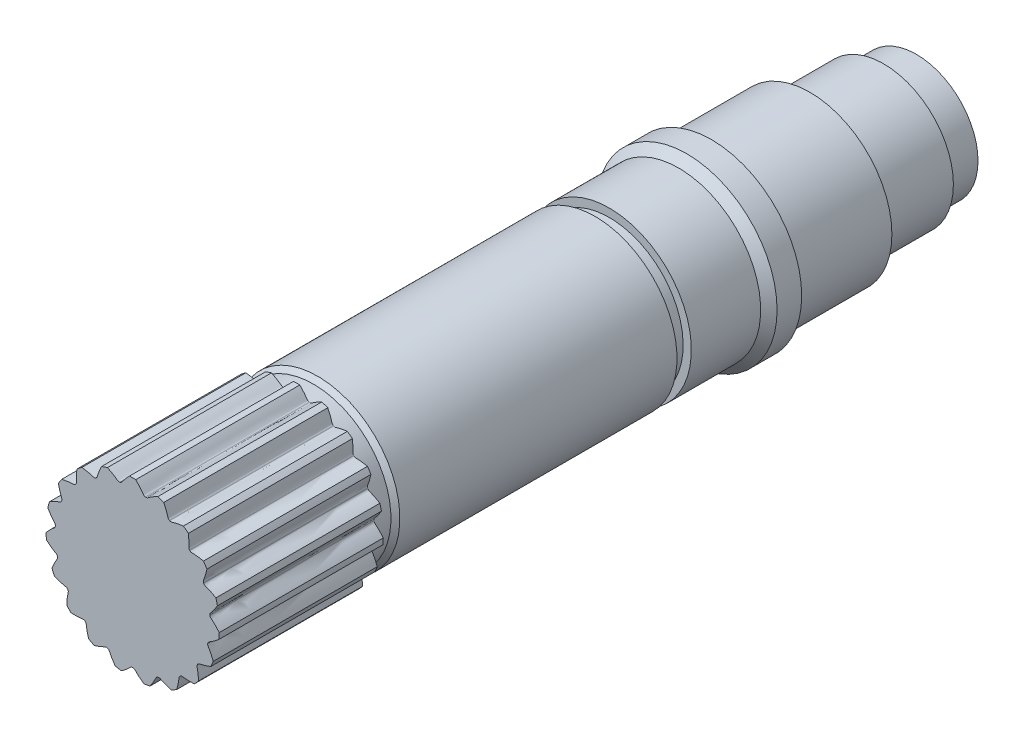
SolidWorks part; units mm, degrees
material "Alloy Steel"
ref_plane "Front Plane" through (0, 0, 0) normal (0, 0, 1) x (1, 0, 0)
ref_plane "Top Plane" through (0, 0, 0) normal (0, 1, 0) x (1, 0, 0)
ref_plane "Right Plane" through (0, 0, 0) normal (1, 0, 0) x (0, 0, -1)
sketch "Sketch12" plane through (0, 0, 0) normal (0, 0, 1) x (1, 0, 0)
  circle A0 centre (0, 0) radius 10
  dimension "D1" = 20
extrude "Shaft" add sketch "Sketch12" along normal mid plane 45
sketch "Sketch13" plane through (0, 0, 22.5) normal (0, 0, 1) x (1, 0, 0)
  circle A0 centre (0, 0) radius 9.4556
  dimension "D1" = 18.9113
extrude "Motor side relief" add sketch "Sketch13" along normal blind 1.587
sketch "Sketch14" plane through (0, 0, -22.5) normal (0, 0, -1) x (-1, 0, 0)
  circle A0 centre (0, 0) radius 8.3981
  dimension "D1" = 16.7963
sketch "Sketch15" plane through (0, 0, 24.087) normal (0, 0, 1) x (1, 0, 0)
  line L0 (5.7898, -7.4758) -> (5.8078, -7.4618)
  line L1 (5.8078, -7.4618) -> (5.8257, -7.4478)
  line L2 (7.9035, -5.1908) -> (7.9159, -5.1717)
  line L3 (7.9159, -5.1717) -> (7.9284, -5.1527)
  line L4 (9.1607, -2.3432) -> (9.1663, -2.3212)
  line L5 (9.1663, -2.3212) -> (9.1719, -2.2992)
  line L6 (9.4252, 0.7582) -> (9.4233, 0.7808)
  line L7 (9.4233, 0.7808) -> (9.4214, 0.8035)
  line L8 (8.6683, 3.7775) -> (8.6592, 3.7983)
  line L9 (8.6592, 3.7983) -> (8.6501, 3.8191)
  line L10 (6.9721, 6.3874) -> (6.9567, 6.4041)
  line L11 (6.9567, 6.4041) -> (6.9413, 6.4208)
  line L12 (4.5204, 8.3051) -> (4.5004, 8.316)
  line L13 (4.5004, 8.316) -> (4.4804, 8.3268)
  line L14 (1.5788, 9.3229) -> (1.5563, 9.3267)
  line L15 (1.5563, 9.3267) -> (1.5339, 9.3304)
  line L16 (-1.5339, 9.3304) -> (-1.5563, 9.3267)
  line L17 (-1.5563, 9.3267) -> (-1.5788, 9.3229)
  line L18 (-4.4804, 8.3268) -> (-4.5004, 8.316)
  line L19 (-4.5004, 8.316) -> (-4.5204, 8.3051)
  line L20 (-6.9413, 6.4208) -> (-6.9567, 6.4041)
  line L21 (-6.9567, 6.4041) -> (-6.9721, 6.3874)
  line L22 (-8.6501, 3.8191) -> (-8.6592, 3.7983)
  line L23 (-8.6592, 3.7983) -> (-8.6683, 3.7775)
  line L24 (-9.4214, 0.8035) -> (-9.4233, 0.7808)
  line L25 (-9.4233, 0.7808) -> (-9.4252, 0.7582)
  line L26 (-9.1719, -2.2992) -> (-9.1663, -2.3212)
  line L27 (-9.1663, -2.3212) -> (-9.1607, -2.3432)
  line L28 (-7.9284, -5.1527) -> (-7.9159, -5.1717)
  line L29 (-7.9159, -5.1717) -> (-7.9035, -5.1908)
  line L30 (-5.8257, -7.4478) -> (-5.8078, -7.4618)
  line L31 (-5.8078, -7.4618) -> (-5.7898, -7.4758)
  line L32 (-3.0917, -8.9359) -> (-3.0702, -8.9433)
  line L33 (-3.0702, -8.9433) -> (-3.0487, -8.9507)
  line L34 (-0.0227, -9.4556) -> (0, -9.4556)
  line L35 (0, -9.4556) -> (0.0227, -9.4556)
  line L36 (3.0487, -8.9507) -> (3.0702, -8.9433)
  line L37 (3.0702, -8.9433) -> (3.0917, -8.9359)
  arc A0 (4.6925, -9.4774) -> (5.3676, -9.1121) centre (0, 0) ccw
  arc A1 (7.5156, -7.4402) -> (8.0355, -6.8755) centre (0, 0) ccw
  arc A2 (9.5242, -4.5968) -> (9.8326, -3.8939) centre (0, 0) ccw
  arc A3 (10.5007, -1.2552) -> (10.5641, -0.4903) centre (0, 0) ccw
  arc A4 (10.3394, 2.2224) -> (10.1509, 2.9665) centre (0, 0) ccw
  arc A5 (9.0575, 5.4591) -> (8.6377, 6.1017) centre (0, 0) ccw
  arc A6 (6.7942, 8.1043) -> (6.1885, 8.5758) centre (0, 0) ccw
  arc A7 (3.7946, 9.8713) -> (3.0686, 10.1205) centre (0, 0) ccw
  arc A8 (0.3838, 10.5685) -> (-0.3838, 10.5685) centre (0, 0) ccw
  arc A9 (-3.0686, 10.1205) -> (-3.7946, 9.8713) centre (0, 0) ccw
  arc A10 (-6.1885, 8.5758) -> (-6.7942, 8.1043) centre (0, 0) ccw
  arc A11 (-8.6377, 6.1017) -> (-9.0575, 5.4591) centre (0, 0) ccw
  arc A12 (-10.1509, 2.9665) -> (-10.3394, 2.2224) centre (0, 0) ccw
  arc A13 (-10.5641, -0.4903) -> (-10.5007, -1.2552) centre (0, 0) ccw
  arc A14 (-9.8326, -3.8939) -> (-9.5242, -4.5968) centre (0, 0) ccw
  arc A15 (-8.0355, -6.8755) -> (-7.5156, -7.4402) centre (0, 0) ccw
  arc A16 (-5.3676, -9.1121) -> (-4.6925, -9.4774) centre (0, 0) ccw
  arc A17 (-2.1181, -10.3612) -> (-1.361, -10.4876) centre (0, 0) ccw
  arc A18 (1.361, -10.4876) -> (2.1181, -10.3612) centre (0, 0) ccw
  spline S0 degree 3 poles (3.0917, -8.9359) (3.1544, -8.9142) (3.2184, -8.911) (3.3396, -8.938) (3.397, -8.9729) (3.5767, -9.0624) (3.828, -9.1783) (4.24, -9.3384) (4.5379, -9.4334) (4.6925, -9.4774) knots 0 0 0 0 0.125 0.125 0.25 0.25 0.5 0.75 1 1 1 1
  spline S1 degree 3 poles (5.3676, -9.1121) (5.4153, -8.9586) (5.4987, -8.6572) (5.5901, -8.2247) (5.6305, -7.951) (5.6538, -7.7516) (5.656, -7.6845) (5.6997, -7.5682) (5.7374, -7.5164) (5.7898, -7.4758) knots 0 0 0 0 0.25 0.5 0.75 0.75 0.875 0.875 1 1 1 1
  spline S2 degree 3 poles (5.8257, -7.4478) (5.8779, -7.407) (5.9374, -7.3832) (6.0608, -7.3694) (6.1265, -7.3837) (6.3255, -7.41) (6.6008, -7.438) (7.0425, -7.4557) (7.3551, -7.4488) (7.5156, -7.4402) knots 0 0 0 0 0.125 0.125 0.25 0.25 0.5 0.75 1 1 1 1
  spline S3 degree 3 poles (8.0355, -6.8755) (8.0308, -6.7148) (8.0117, -6.4027) (7.9577, -5.964) (7.9071, -5.692) (7.8645, -5.4958) (7.8447, -5.4316) (7.8483, -5.3075) (7.8671, -5.2462) (7.9035, -5.1908) knots 0 0 0 0 0.25 0.5 0.75 0.75 0.875 0.875 1 1 1 1
  spline S4 degree 3 poles (7.9284, -5.1527) (7.9645, -5.0971) (8.013, -5.0552) (8.1253, -5.0021) (8.192, -4.9944) (8.3888, -4.9546) (8.6583, -4.8918) (9.0817, -4.765) (9.3752, -4.6571) (9.5242, -4.5968) knots 0 0 0 0 0.125 0.125 0.25 0.25 0.5 0.75 1 1 1 1
  spline S5 degree 3 poles (9.8326, -3.8939) (9.7759, -3.7434) (9.6566, -3.4544) (9.4631, -3.057) (9.3268, -2.8161) (9.2228, -2.6445) (9.1833, -2.5901) (9.1463, -2.4716) (9.1443, -2.4075) (9.1607, -2.3432) knots 0 0 0 0 0.25 0.5 0.75 0.75 0.875 0.875 1 1 1 1
  spline S6 degree 3 poles (9.1719, -2.2992) (9.188, -2.2349) (9.2203, -2.1795) (9.3092, -2.0928) (9.3699, -2.0638) (9.543, -1.9624) (9.7775, -1.8154) (10.1368, -1.558) (10.3793, -1.3606) (10.5007, -1.2552) knots 0 0 0 0 0.125 0.125 0.25 0.25 0.5 0.75 1 1 1 1
  spline S7 degree 3 poles (10.5641, -0.4903) (10.4617, -0.3663) (10.255, -0.1317) (9.9429, 0.1813) (9.7359, 0.3649) (9.5818, 0.4935) (9.5267, 0.532) (9.4533, 0.6322) (9.4305, 0.6921) (9.4252, 0.7582) knots 0 0 0 0 0.25 0.5 0.75 0.75 0.875 0.875 1 1 1 1
  spline S8 degree 3 poles (9.4214, 0.8035) (9.4158, 0.8695) (9.4284, 0.9324) (9.4844, 1.0433) (9.5323, 1.0904) (9.6631, 1.2426) (9.8372, 1.4577) (10.0935, 1.8179) (10.2588, 2.0833) (10.3394, 2.2224) knots 0 0 0 0 0.125 0.125 0.25 0.25 0.5 0.75 1 1 1 1
  spline S9 degree 3 poles (10.1509, 2.9665) (10.0138, 3.0504) (9.7422, 3.2052) (9.3453, 3.4) (9.0899, 3.5063) (8.9024, 3.5779) (8.8378, 3.5965) (8.7358, 3.6674) (8.6948, 3.7167) (8.6683, 3.7775) knots 0 0 0 0 0.25 0.5 0.75 0.75 0.875 0.875 1 1 1 1
  spline S10 degree 3 poles (8.6501, 3.8191) (8.6233, 3.8797) (8.6148, 3.9433) (8.6317, 4.0663) (8.6618, 4.1264) (8.7361, 4.3129) (8.8308, 4.5729) (8.9563, 4.9967) (9.0265, 5.3014) (9.0575, 5.4591) knots 0 0 0 0 0.125 0.125 0.25 0.25 0.5 0.75 1 1 1 1
  spline S11 degree 3 poles (8.6377, 6.1017) (8.4808, 6.1366) (8.1736, 6.1948) (7.735, 6.2502) (7.4588, 6.2678) (7.2583, 6.2747) (7.1911, 6.2713) (7.0717, 6.3052) (7.0169, 6.3385) (6.9721, 6.3874) knots 0 0 0 0 0.25 0.5 0.75 0.75 0.875 0.875 1 1 1 1
  spline S12 degree 3 poles (6.9413, 6.4208) (6.8963, 6.4695) (6.8676, 6.5268) (6.8437, 6.6487) (6.8526, 6.7153) (6.8624, 6.9158) (6.8676, 7.1925) (6.8486, 7.6341) (6.816, 7.9451) (6.7942, 8.1043) knots 0 0 0 0 0.125 0.125 0.25 0.25 0.5 0.75 1 1 1 1
  spline S13 degree 3 poles (6.1885, 8.5758) (6.0287, 8.5578) (5.7193, 8.5131) (5.2865, 8.4231) (5.0196, 8.3501) (4.8276, 8.2914) (4.7652, 8.2664) (4.6412, 8.2597) (4.5786, 8.2734) (4.5204, 8.3051) knots 0 0 0 0 0.25 0.5 0.75 0.75 0.875 0.875 1 1 1 1
  spline S14 degree 3 poles (4.4804, 8.3268) (4.422, 8.3582) (4.3763, 8.4031) (4.3141, 8.5106) (4.3009, 8.5765) (4.245, 8.7693) (4.1601, 9.0326) (3.9988, 9.4442) (3.8669, 9.7277) (3.7946, 9.8713) knots 0 0 0 0 0.125 0.125 0.25 0.25 0.5 0.75 1 1 1 1
  spline S15 degree 3 poles (3.0686, 10.1205) (2.9233, 10.0517) (2.6452, 9.9089) (2.2651, 9.6832) (2.0363, 9.5275) (1.8738, 9.4097) (1.8229, 9.3658) (1.7078, 9.3192) (1.6441, 9.3118) (1.5788, 9.3229) knots 0 0 0 0 0.25 0.5 0.75 0.75 0.875 0.875 1 1 1 1
  spline S16 degree 3 poles (1.5339, 9.3304) (1.4685, 9.3411) (1.4107, 9.3688) (1.3169, 9.4502) (1.283, 9.5083) (1.1676, 9.6725) (1.0018, 9.894) (0.7156, 10.2309) (0.4988, 10.4563) (0.3838, 10.5685) knots 0 0 0 0 0.125 0.125 0.25 0.25 0.5 0.75 1 1 1 1
  spline S17 degree 3 poles (-0.3838, 10.5685) (-0.4988, 10.4563) (-0.7156, 10.2309) (-1.0018, 9.894) (-1.1676, 9.6725) (-1.283, 9.5083) (-1.3169, 9.4502) (-1.4107, 9.3688) (-1.4685, 9.3411) (-1.5339, 9.3304) knots 0 0 0 0 0.25 0.5 0.75 0.75 0.875 0.875 1 1 1 1
  spline S18 degree 3 poles (-1.5788, 9.3229) (-1.6441, 9.3118) (-1.7078, 9.3192) (-1.8229, 9.3658) (-1.8738, 9.4097) (-2.0363, 9.5275) (-2.2651, 9.6832) (-2.6452, 9.9089) (-2.9233, 10.0517) (-3.0686, 10.1205) knots 0 0 0 0 0.125 0.125 0.25 0.25 0.5 0.75 1 1 1 1
  spline S19 degree 3 poles (-3.7946, 9.8713) (-3.8669, 9.7277) (-3.9988, 9.4442) (-4.1601, 9.0326) (-4.245, 8.7693) (-4.3009, 8.5765) (-4.3141, 8.5106) (-4.3763, 8.4031) (-4.422, 8.3582) (-4.4804, 8.3268) knots 0 0 0 0 0.25 0.5 0.75 0.75 0.875 0.875 1 1 1 1
  spline S20 degree 3 poles (-4.5204, 8.3051) (-4.5786, 8.2734) (-4.6412, 8.2597) (-4.7652, 8.2664) (-4.8276, 8.2914) (-5.0196, 8.3501) (-5.2865, 8.4231) (-5.7193, 8.5131) (-6.0287, 8.5578) (-6.1885, 8.5758) knots 0 0 0 0 0.125 0.125 0.25 0.25 0.5 0.75 1 1 1 1
  spline S21 degree 3 poles (-6.7942, 8.1043) (-6.816, 7.9451) (-6.8486, 7.6341) (-6.8676, 7.1925) (-6.8624, 6.9158) (-6.8526, 6.7153) (-6.8437, 6.6487) (-6.8676, 6.5268) (-6.8963, 6.4695) (-6.9413, 6.4208) knots 0 0 0 0 0.25 0.5 0.75 0.75 0.875 0.875 1 1 1 1
  spline S22 degree 3 poles (-6.9721, 6.3874) (-7.0169, 6.3385) (-7.0717, 6.3052) (-7.1911, 6.2713) (-7.2583, 6.2747) (-7.4588, 6.2678) (-7.735, 6.2502) (-8.1736, 6.1948) (-8.4808, 6.1366) (-8.6377, 6.1017) knots 0 0 0 0 0.125 0.125 0.25 0.25 0.5 0.75 1 1 1 1
  spline S23 degree 3 poles (-9.0575, 5.4591) (-9.0265, 5.3014) (-8.9563, 4.9967) (-8.8308, 4.5729) (-8.7361, 4.3129) (-8.6618, 4.1264) (-8.6317, 4.0663) (-8.6148, 3.9433) (-8.6233, 3.8797) (-8.6501, 3.8191) knots 0 0 0 0 0.25 0.5 0.75 0.75 0.875 0.875 1 1 1 1
  spline S24 degree 3 poles (-8.6683, 3.7775) (-8.6948, 3.7167) (-8.7358, 3.6674) (-8.8378, 3.5965) (-8.9024, 3.5779) (-9.0899, 3.5063) (-9.3453, 3.4) (-9.7422, 3.2052) (-10.0138, 3.0504) (-10.1509, 2.9665) knots 0 0 0 0 0.125 0.125 0.25 0.25 0.5 0.75 1 1 1 1
  spline S25 degree 3 poles (-10.3394, 2.2224) (-10.2588, 2.0833) (-10.0935, 1.8179) (-9.8372, 1.4577) (-9.6631, 1.2426) (-9.5323, 1.0904) (-9.4844, 1.0433) (-9.4284, 0.9324) (-9.4158, 0.8695) (-9.4214, 0.8035) knots 0 0 0 0 0.25 0.5 0.75 0.75 0.875 0.875 1 1 1 1
  spline S26 degree 3 poles (-9.4252, 0.7582) (-9.4305, 0.6921) (-9.4533, 0.6322) (-9.5267, 0.532) (-9.5818, 0.4935) (-9.7359, 0.3649) (-9.9429, 0.1813) (-10.255, -0.1317) (-10.4617, -0.3663) (-10.5641, -0.4903) knots 0 0 0 0 0.125 0.125 0.25 0.25 0.5 0.75 1 1 1 1
  spline S27 degree 3 poles (-10.5007, -1.2552) (-10.3793, -1.3606) (-10.1368, -1.558) (-9.7775, -1.8154) (-9.543, -1.9624) (-9.3699, -2.0638) (-9.3092, -2.0928) (-9.2203, -2.1795) (-9.188, -2.2349) (-9.1719, -2.2992) knots 0 0 0 0 0.25 0.5 0.75 0.75 0.875 0.875 1 1 1 1
  spline S28 degree 3 poles (-9.1607, -2.3432) (-9.1443, -2.4075) (-9.1463, -2.4716) (-9.1833, -2.5901) (-9.2228, -2.6445) (-9.3268, -2.8161) (-9.4631, -3.057) (-9.6566, -3.4544) (-9.7759, -3.7434) (-9.8326, -3.8939) knots 0 0 0 0 0.125 0.125 0.25 0.25 0.5 0.75 1 1 1 1
  spline S29 degree 3 poles (-9.5242, -4.5968) (-9.3752, -4.6571) (-9.0817, -4.765) (-8.6583, -4.8918) (-8.3888, -4.9546) (-8.192, -4.9944) (-8.1253, -5.0021) (-8.013, -5.0552) (-7.9645, -5.0971) (-7.9284, -5.1527) knots 0 0 0 0 0.25 0.5 0.75 0.75 0.875 0.875 1 1 1 1
  spline S30 degree 3 poles (-7.9035, -5.1908) (-7.8671, -5.2462) (-7.8483, -5.3075) (-7.8447, -5.4316) (-7.8645, -5.4958) (-7.9071, -5.692) (-7.9577, -5.964) (-8.0117, -6.4027) (-8.0308, -6.7148) (-8.0355, -6.8755) knots 0 0 0 0 0.125 0.125 0.25 0.25 0.5 0.75 1 1 1 1
  spline S31 degree 3 poles (-7.5156, -7.4402) (-7.3551, -7.4488) (-7.0425, -7.4557) (-6.6008, -7.438) (-6.3255, -7.41) (-6.1265, -7.3837) (-6.0608, -7.3694) (-5.9374, -7.3832) (-5.8779, -7.407) (-5.8257, -7.4478) knots 0 0 0 0 0.25 0.5 0.75 0.75 0.875 0.875 1 1 1 1
  spline S32 degree 3 poles (-5.7898, -7.4758) (-5.7374, -7.5164) (-5.6997, -7.5682) (-5.656, -7.6845) (-5.6538, -7.7516) (-5.6305, -7.951) (-5.5901, -8.2247) (-5.4987, -8.6572) (-5.4153, -8.9586) (-5.3676, -9.1121) knots 0 0 0 0 0.125 0.125 0.25 0.25 0.5 0.75 1 1 1 1
  spline S33 degree 3 poles (-4.6925, -9.4774) (-4.5379, -9.4334) (-4.24, -9.3384) (-3.828, -9.1783) (-3.5767, -9.0624) (-3.397, -8.9729) (-3.3396, -8.938) (-3.2184, -8.911) (-3.1544, -8.9142) (-3.0917, -8.9359) knots 0 0 0 0 0.25 0.5 0.75 0.75 0.875 0.875 1 1 1 1
  spline S34 degree 3 poles (-3.0487, -8.9507) (-2.986, -8.972) (-2.9335, -9.0088) (-2.8544, -9.1046) (-2.8306, -9.1674) (-2.7437, -9.3484) (-2.6166, -9.5942) (-2.3898, -9.9736) (-2.2131, -10.2315) (-2.1181, -10.3612) knots 0 0 0 0 0.125 0.125 0.25 0.25 0.5 0.75 1 1 1 1
  spline S35 degree 3 poles (-1.361, -10.4876) (-1.229, -10.3957) (-0.9781, -10.2091) (-0.6404, -9.9239) (-0.4404, -9.7327) (-0.2995, -9.5898) (-0.2565, -9.5381) (-0.1506, -9.4732) (-0.089, -9.4555) (-0.0227, -9.4556) knots 0 0 0 0 0.25 0.5 0.75 0.75 0.875 0.875 1 1 1 1
  spline S36 degree 3 poles (0.0227, -9.4556) (0.089, -9.4555) (0.1506, -9.4732) (0.2565, -9.5381) (0.2995, -9.5898) (0.4404, -9.7327) (0.6404, -9.9239) (0.9781, -10.2091) (1.229, -10.3957) (1.361, -10.4876) knots 0 0 0 0 0.125 0.125 0.25 0.25 0.5 0.75 1 1 1 1
  spline S37 degree 3 poles (2.1181, -10.3612) (2.2131, -10.2315) (2.3898, -9.9736) (2.6166, -9.5942) (2.7437, -9.3484) (2.8306, -9.1674) (2.8544, -9.1046) (2.9335, -9.0088) (2.986, -8.972) (3.0487, -8.9507) knots 0 0 0 0 0.25 0.5 0.75 0.75 0.875 0.875 1 1 1 1
extrude "Motor spline" add sketch "Sketch15" along normal blind 20
chamfer "Chamfer3" distance 1 angle 45 1 edges at (10, 0, 22.5)
sketch "Sketch23" plane through (0, 0, -32.5) normal (-0.9227, 0.3855, 0) x (-0.3855, -0.9227, 0)
  line L0 (10, 20.2042) -> (9, 20.2042)
  line L1 (9, 20.2042) -> (9, 18.4542)
  line L2 (9, 18.4542) -> (10, 18.4542)
  line L3 (10, 18.4542) -> (10, 20.2042)
  line L4 (10, 10) -> (10, 54) construction
  line L5 (-13.85, 20.2042) -> (13.85, 20.2042) construction
  line L7 (0, 185.3358) -> (0, -121.609) construction
  dimension "D1" = 1.75
  dimension "D2" = 1
revolve "snap ring" cut sketch "Sketch23" angle 360 about L7
sketch "Sketch24" plane through (0, 0, 0) normal (0, 1, 0) x (1, 0, 0)
  line L0 (10, 22.5) -> (11, 23.5)
  line L1 (11, 23.5) -> (11, 26.5)
  line L2 (11, 26.5) -> (10, 26.5)
  line L3 (10, 26.5) -> (10, 38.5)
  line L4 (10, 38.5) -> (8.5, 38.5)
  line L5 (7.5, 47.5) -> (7.5, 51.5)
  line L6 (7.5, 51.5) -> (0, 51.5)
  line L7 (0, 51.5) -> (0, 22.5)
  line L8 (10, 22.5) -> (-10, 22.5) construction
  line L9 (0, 22.5) -> (10, 22.5)
  line L10 (0, 0) -> (0, 49.7252) construction
  line L11 (10, 14.0458) -> (10, 22.5) construction
  line L12 (7.5, 47.5) -> (8.5, 47.5)
  line L13 (8.5, 47.5) -> (8.5, 38.5)
  dimension "D1" = 15
  dimension "D2" = 17
  dimension "D3" = 20
  dimension "D4" = 12
  dimension "D5" = 135
  dimension "D6" = 22
  dimension "D7" = 3
  dimension "D8" = 4
  dimension "D9" = 9
revolve "Revolve1" add sketch "Sketch24" angle 360 about L10
